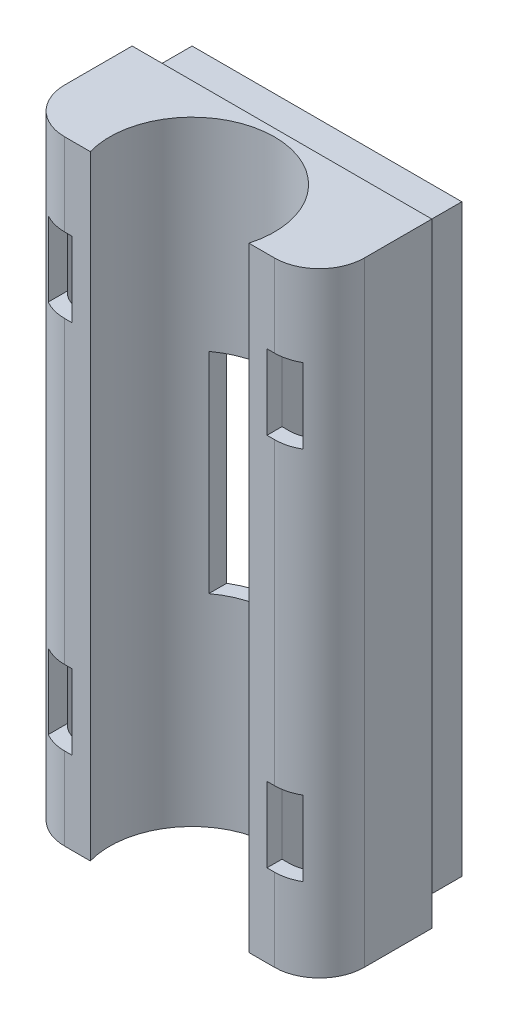
SolidWorks part; units mm, degrees
ref_plane "Front Plane" through (0, 0, 0) normal (0, 0, 1) x (1, 0, 0)
ref_plane "Top Plane" through (0, 0, 0) normal (0, 1, 0) x (1, 0, 0)
ref_plane "Right Plane" through (0, 0, 0) normal (1, 0, 0) x (0, 0, -1)
sketch "Sketch1" plane through (0, 0, 0) normal (0, 1, 0) x (1, 0, 0)
  line L0 (-20, 12) -> (-20, 3)
  line L1 (-20, 12) -> (-18, 12)
  line L2 (-18, 12) -> (-18, 18)
  line L3 (-18, 18) -> (18, 18)
  line L4 (18, 18) -> (18, 12)
  line L5 (18, 12) -> (20, 12)
  line L6 (-14, -3) -> (-10.583, -3)
  line L7 (20, 12) -> (20, 3)
  line L8 (14, -3) -> (10.583, -3)
  arc A0 (10.583, -3) -> (-10.583, -3) centre (0, 0) ccw
  arc A1 (20, 3) -> (14, -3) centre (14, 3) cw
  arc A2 (-20, 3) -> (-14, -3) centre (-14, 3) ccw
  point P5 (0, 0)
  point P14 (0, 18)
  point P15 (0, 0)
  dimension "D1" = 22
  dimension "D8" = 6
  dimension "D2" = 40
  dimension "D3" = 2
  dimension "D4" = 2
  dimension "D5" = 6
  dimension "D6" = 12
  dimension "D7" = 3
extrude "Boss-Extrude1" add sketch "Sketch1" along normal blind 82
sketch "Sketch2" plane through (0, 0, 0) normal (1, 0, 0) x (0, 0, -1)
  line L0 (12, 82) -> (12, 0) construction
  line L1 (18, 82) -> (12, 82)
  line L2 (18, 82) -> (18, 80)
  line L3 (18, 80) -> (12, 80)
  line L4 (12, 82) -> (12, 80)
  line L5 (12, 82) -> (12, 0) construction
  line L6 (18, 0) -> (12, 0)
  line L7 (18, 0) -> (18, 2)
  line L8 (18, 2) -> (12, 2)
  line L9 (12, 0) -> (12, 2)
  dimension "D1" = 2
  dimension "D2" = 2
extrude "Cut-Extrude1" cut sketch "Sketch2" against normal blind 30 and the other way blind 30
shell "Shell1" thickness 2 removed face at (0, 41, -18)
sketch "Sketch3" plane through (0, 0, 0) normal (0, 0, 1) x (1, 0, 0)
  line L0 (0, 0) -> (0, 82) construction
  line L1 (11, 82) -> (-11, 82) construction
  line L2 (0, 41) -> (-10.583, 41) construction
  line L3 (-10.583, 82) -> (-10.583, 0) construction
  line L4 (-20, 82) -> (-20, 0) construction
  line L5 (-13, 21) -> (-17, 21)
  line L6 (-13, 21) -> (-13, 11)
  line L7 (-13, 11) -> (-17, 11)
  line L8 (-17, 21) -> (-17, 11)
  line L9 (13, 11) -> (17, 11)
  line L10 (13, 21) -> (17, 21)
  line L11 (17, 21) -> (17, 11)
  line L12 (13, 21) -> (13, 11)
  line L13 (13, 61) -> (13, 71)
  line L14 (17, 61) -> (17, 71)
  line L15 (13, 61) -> (17, 61)
  line L16 (13, 71) -> (17, 71)
  line L17 (-17, 61) -> (-17, 71)
  line L18 (-13, 71) -> (-17, 71)
  line L19 (-13, 61) -> (-13, 71)
  line L20 (-13, 61) -> (-17, 61)
  dimension "D1" = 3
  dimension "D2" = 4
  dimension "D3" = 10
  dimension "D4" = 20
extrude "Cut-Extrude2" cut sketch "Sketch3" against normal blind 6 and the other way blind 6
sketch "Sketch4" plane through (0, 0, 0) normal (0, 0, 1) x (1, 0, 0)
  line L0 (-17, 21) -> (-14, 21) construction
  line L1 (-6.583, 55) -> (6.583, 55)
  line L2 (-6.583, 55) -> (-6.583, 27)
  line L3 (-6.583, 27) -> (6.583, 27)
  line L4 (6.583, 55) -> (6.583, 27)
  line L9 (17, 61) -> (14, 61) construction
  line L10 (-10.583, 82) -> (-10.583, 0) construction
  line L11 (10.583, 82) -> (10.583, 0) construction
  dimension "D1" = 6
  dimension "D2" = 6
  dimension "D3" = 4
  dimension "D4" = 4
extrude "Cut-Extrude3" cut sketch "Sketch4" against normal blind 20
